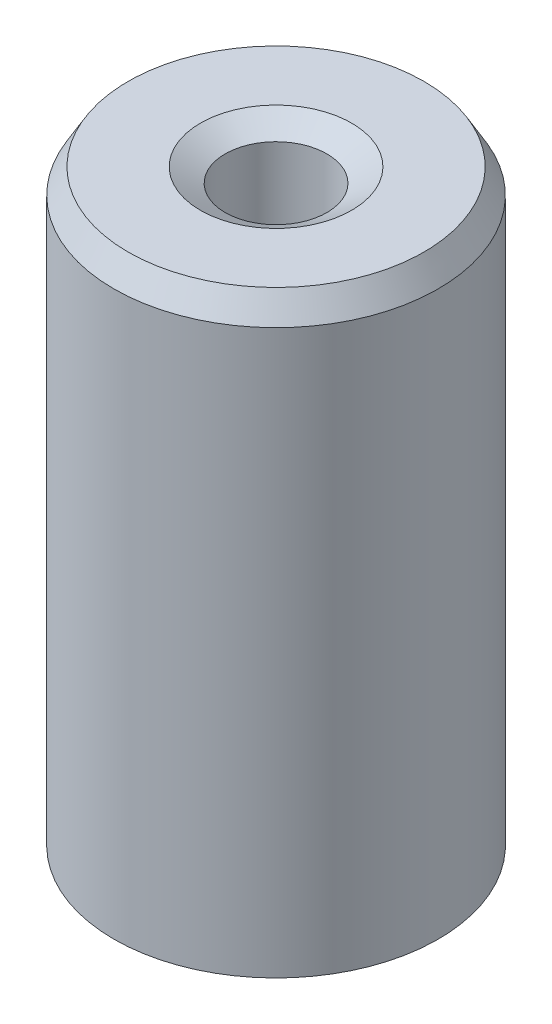
SolidWorks part; units mm, degrees
ref_plane "Front Plane" through (0, 0, 0) normal (0, 0, 1) x (1, 0, 0)
ref_plane "Top Plane" through (0, 0, 0) normal (0, 1, 0) x (1, 0, 0)
ref_plane "Right Plane" through (0, 0, 0) normal (1, 0, 0) x (0, 0, -1)
sketch "Sketch1" plane through (0, 0, 0) normal (0, 1, 0) x (1, 0, 0)
  circle A0 centre (0, 0) radius 7.5
  dimension "SLEEVE_OD" = 15
extrude "Boss-Extrude1" add sketch "Sketch1" along normal blind 27.8512
sketch "Sketch2" plane through (0, 0, 0) normal (0, 1, 0) x (1, 0, 0)
  circle A0 centre (0, 0) radius 2.3523
  dimension "BORE_D" = 4.7046
extrude "Cut-Extrude1" cut sketch "Sketch2" along normal through all
chamfer "Chamfer1" distance 1.1439 angle 30 4 edges at (0, 27.8512, 2.3523) (0, 0, 2.3523) (0, 0, 7.5) (0, 27.8512, 7.5) first distance on face at (0, 27.8512, 2.3523) first distance on face at (0, 0, 2.3523) first distance on face at (0, 27.8512, 7.5)
